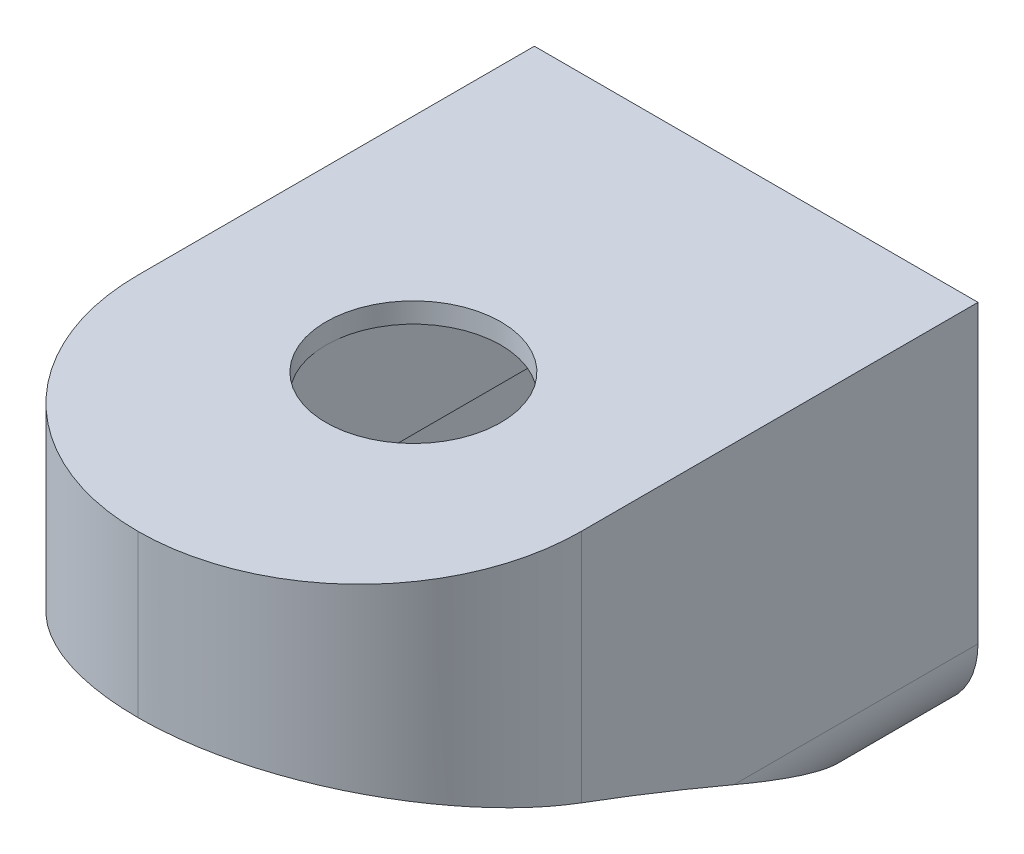
SolidWorks part; units mm, degrees
ref_plane "Front Plane" through (0, 0, 0) normal (0, 0, 1) x (1, 0, 0)
ref_plane "Top Plane" through (0, 0, 0) normal (0, 1, 0) x (1, 0, 0)
ref_plane "Right Plane" through (0, 0, 0) normal (1, 0, 0) x (0, 0, -1)
sketch "Sketch1" plane through (0, 0, 0) normal (0, 0, 1) x (1, 0, 0)
  line L1 (-16.5, -14) -> (16.5, -14)
  line L2 (-16.5, -14) -> (-16.5, 14)
  line L3 (-16.5, 14) -> (16.5, 14)
  line L4 (16.5, -14) -> (16.5, 14)
  line L5 (-16.5, -14) -> (16.5, 14) construction
  line L6 (-16.5, 14) -> (16.5, -14) construction
  point P0 (0, 0)
  dimension "D1" = 33
  dimension "D2" = 28
extrude "Boss-Extrude1" add sketch "Sketch1" along normal blind 46
sketch "Sketch2" plane through (16.5, 0, 0) normal (1, 0, 0) x (0, 0, -1)
  line L0 (-46, -14) -> (0, -14) construction
  line L1 (-46, -14) -> (-46, 14) construction
  line L2 (-46, 2) -> (-46, -14)
  line L3 (-46, -14) -> (-5, -14)
  line L4 (0, -14) -> (0, 14) construction
  line L5 (-46, 14) -> (0, 14) construction
  spline S0 degree 2 poles (-5, -14) (-24.9039, -4.2615) (-46, 2) knots 0 0 0 1 1 1
  dimension "D1" = 5
  dimension "D2" = 12
extrude "Cut-Extrude1" cut sketch "Sketch2" against normal through all
sketch "Sketch4" plane through (16.5, 0, 0) normal (1, 0, 0) x (0, 0, -1)
  line L0 (-5, -14) -> (-2.5, -14)
  line L1 (-5, -14) -> (0, -14) construction
  line L2 (-2.5, -14) -> (-2.5, 3.5)
  line L3 (-2.5, 3.5) -> (-40.5, 3.5)
  line L4 (-40.5, 3.5) -> (-40.5, 0.302)
  parabola Q0 (-5, -14) -> (-46, 2) focus (-78.1787, -125.7507) apex (-35.5265, -1.348) construction
  parabola Q1 (-5, -14) -> (-46, 2) focus (-78.1787, -125.7507) apex (-35.5265, -1.348) construction
  parabola Q2 (-5, -14) -> (-40.5, 0.302) focus (-78.1787, -125.7507) apex (-35.5265, -1.348)
  dimension "D1" = 17.5
  dimension "D2" = 38
extrude "Cut-Extrude2" cut sketch "Sketch4" against normal blind 27 from offset 3 offset against normal yes
fillet "Fillet2" radius 12.5 2 edges at (-13.5, 1.901, 40.5) (13.5, 1.901, 40.5)
fillet "Fillet3" radius 16.5 2 edges at (-16.5, 8, 46) (16.5, 8, 46)
fillet "Fillet4" radius 6 2 edges at (-16.5, -14, 2.5) (16.5, -14, 2.5)
sketch "Sketch5" plane through (0, 3.5, 0) normal (0, -1, 0) x (1, 0, 0)
  line L0 (0, 46) -> (0, 0) construction
  line L1 (-10.5, 2.5) -> (10.5, 2.5) construction
  line L2 (-6.5, 9) -> (6.5, 9)
  line L3 (-6.5, 9) -> (-6.5, 32)
  line L4 (-6.5, 32) -> (6.5, 32)
  line L5 (6.5, 9) -> (6.5, 32)
  line L6 (-6.5, 9) -> (6.5, 32) construction
  line L7 (-6.5, 32) -> (6.5, 9) construction
  point P4 (0, 20.5)
  dimension "D1" = 6.5
  dimension "D2" = 23
  dimension "D3" = 13
extrude "Cut-Extrude3" cut sketch "Sketch5" against normal blind 9
sketch "Sketch6" plane through (0, 12.5, 0) normal (0, -1, 0) x (1, 0, 0)
  line L0 (0, 32) -> (0, 9) construction
  line L1 (6.5, 32) -> (-6.5, 32) construction
  line L2 (-6.5, 9) -> (6.5, 9) construction
  line L3 (6.5, 32) -> (-6.5, 32) construction
  circle A0 centre (0, 25.5) radius 6.5
  dimension "D1" = 13
extrude "Cut-Extrude4" cut sketch "Sketch6" against normal through all
sketch "Sketch7" plane through (0, 3.5, 0) normal (0, -1, 0) x (1, 0, 0)
  line L0 (-6.5, 20.5) -> (6.5, 20.5) construction
  line L1 (-6.5, 32) -> (-6.5, 9) construction
  line L2 (6.5, 9) -> (6.5, 32) construction
  line L3 (0, 34.0527) -> (0, 6.4527) construction
  circle A0 centre (0, 34.0527) radius 1
  circle A1 centre (0, 6.4527) radius 1
  point P10 (0, 0)
  point P12 (0, 7.7245)
  point P13 (0, 6.2214)
  point P14 (0, 6.4527)
  dimension "D2" = 2
  dimension "D1" = 27.6
extrude "Cut-Extrude6" cut sketch "Sketch7" against normal blind 8
sketch "Sketch8" plane through (0, 0, 0) normal (0, 0, -1) x (-1, 0, 0)
  line L0 (0, 0) -> (-16.5, 0) construction
  line L1 (-16.5, -8) -> (-16.5, 14) construction
  circle A0 centre (-9.5, 0) radius 1.3
  circle A1 centre (-5, 0) radius 2.5
  circle A2 centre (-0.5, 0) radius 1.3
  dimension "D1" = 2.6
  dimension "D2" = 5
  dimension "D3" = 11.5
  dimension "D4" = 9
  dimension "D5" = 4.5
extrude "Cut-Extrude7" cut sketch "Sketch8" against normal up to surface (2.5 mm away) up to face at (0, -7.9645, 2.5)
